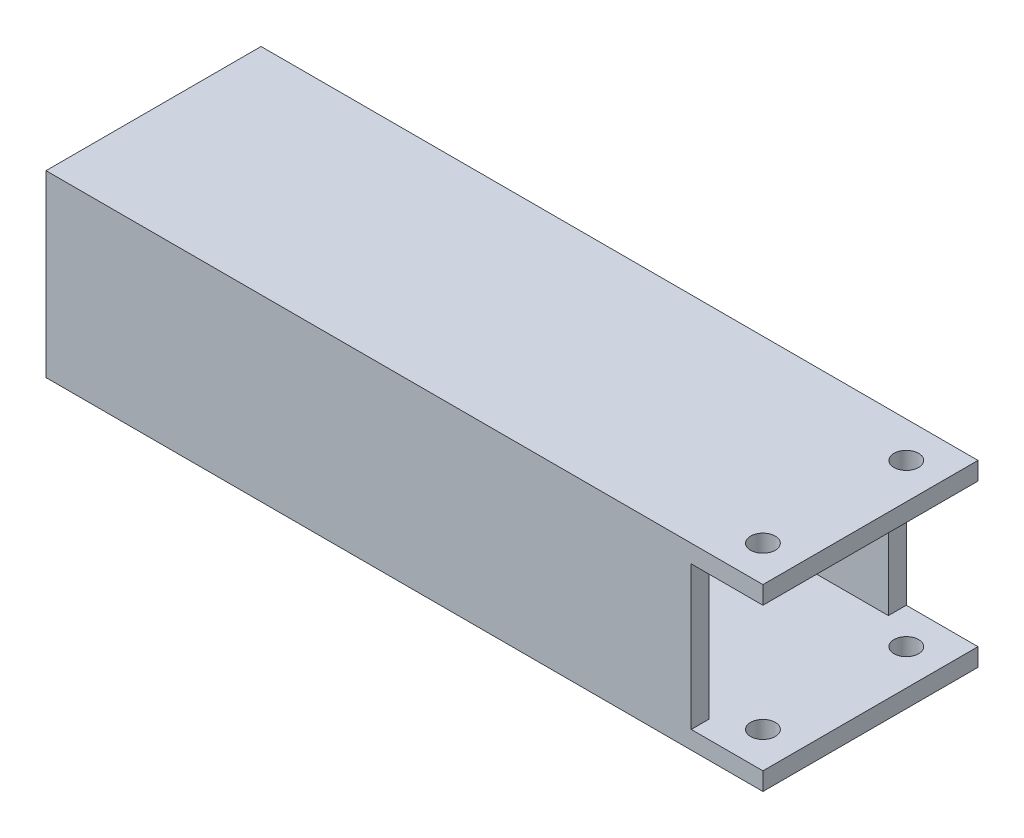
SolidWorks part; units mm, degrees
ref_plane "Front Plane" through (0, 0, 0) normal (0, 0, 1) x (1, 0, 0)
ref_plane "Top Plane" through (0, 0, 0) normal (0, 1, 0) x (1, 0, 0)
ref_plane "Right Plane" through (0, 0, 0) normal (1, 0, 0) x (0, 0, -1)
sketch "Sketch1" plane through (0, 0, 0) normal (0, 1, 0) x (1, 0, 0)
  line L1 (-39.7876, 8.6878) -> (87.2124, 8.6878)
  line L2 (-39.7876, 8.6878) -> (-39.7876, -29.4122)
  line L3 (-39.7876, -29.4122) -> (87.2124, -29.4122)
  line L4 (87.2124, 8.6878) -> (87.2124, -29.4122)
  dimension "D1" = 127
  dimension "D2" = 38.1
extrude "Boss-Extrude4" add sketch "Sketch1" along normal blind 31.75
sketch "Sketch6" plane through (0, 31.75, 0) normal (0, 1, 0) x (1, 0, 0)
  line L0 (87.2124, -29.4122) -> (87.2124, 8.6878) construction
  line L2 (80.8624, 8.6878) -> (80.8624, -29.4122) construction
  line L3 (87.2124, 8.6878) -> (-39.7876, 8.6878) construction
  line L4 (-39.7876, -29.4122) -> (87.2124, -29.4122) construction
  line L5 (-39.7876, -10.3622) -> (87.2124, -10.3622) construction
  line L6 (-39.7876, 8.6878) -> (-39.7876, -29.4122) construction
  circle A0 centre (80.8624, 2.3378) radius 2.1828
  circle A1 centre (80.8624, -23.0622) radius 2.1828
  dimension "D3" = 12.7
  dimension "D2" = 4.3656
  dimension "D1" = 6.35
extrude "Cut-Extrude2" cut sketch "Sketch6" against normal through all
sketch "Sketch8" plane through (0, 0, 29.4122) normal (0, 0, 1) x (1, 0, 0)
  line L0 (87.2124, 31.75) -> (87.2124, 0) construction
  line L1 (87.2124, 28.575) -> (74.5124, 28.575)
  line L2 (87.2124, 28.575) -> (87.2124, 3.175)
  line L3 (87.2124, 3.175) -> (74.5124, 3.175)
  line L4 (74.5124, 28.575) -> (74.5124, 3.175)
  line L5 (-39.7876, 31.75) -> (87.2124, 31.75) construction
  dimension "D1" = 25.4
  dimension "D2" = 12.7
  dimension "D3" = 3.175
extrude "Cut-Extrude4" cut sketch "Sketch8" against normal through all
sketch "Sketch9" plane through (-39.7876, 0, 0) normal (-1, 0, 0) x (0, 0, 1)
  line L0 (10.3622, 31.75) -> (10.3622, 0) construction
  line L1 (-8.6878, 31.75) -> (29.4122, 31.75) construction
  line L2 (-8.6878, 0) -> (29.4122, 0) construction
  line L3 (-8.6878, 15.875) -> (29.4122, 15.875) construction
  line L4 (-8.6878, 31.75) -> (-8.6878, 0) construction
  line L5 (29.4122, 31.75) -> (29.4122, 0) construction
  line L7 (-5.5128, 28.575) -> (26.2372, 28.575)
  line L8 (-5.5128, 28.575) -> (-5.5128, 3.175)
  line L9 (-5.5128, 3.175) -> (26.2372, 3.175)
  line L10 (26.2372, 28.575) -> (26.2372, 3.175)
  line L11 (-5.5128, 28.575) -> (26.2372, 3.175) construction
  line L12 (-5.5128, 3.175) -> (26.2372, 28.575) construction
  point P12 (10.3622, 15.875)
  dimension "D1" = 25.4
  dimension "D2" = 31.75
extrude "Cut-Extrude5" cut sketch "Sketch9" against normal through all
